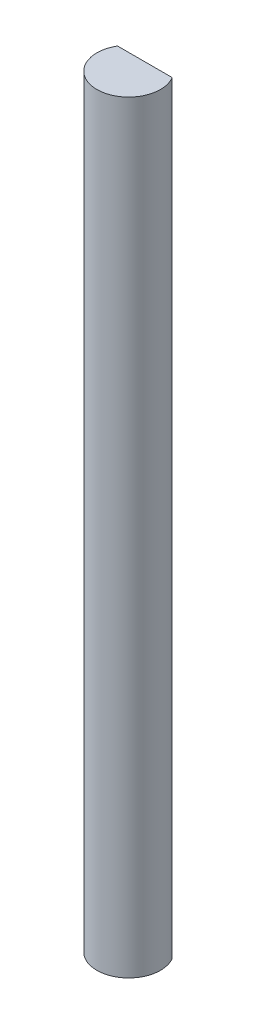
SolidWorks part; units mm, degrees
ref_plane "Front Plane" through (0, 0, 0) normal (0, 0, 1) x (1, 0, 0)
ref_plane "Top Plane" through (0, 0, 0) normal (0, 1, 0) x (1, 0, 0)
ref_plane "Right Plane" through (0, 0, 0) normal (1, 0, 0) x (0, 0, -1)
sketch "Sketch1" plane through (0, 0, 0) normal (0, 1, 0) x (1, 0, 0)
  line L0 (-2.7309, 1.6195) -> (2.7309, 1.6195)
  circle A0 centre (0, 0) radius 3.175
  dimension "D1" = 6.35
  dimension "D2" = 1.6195
extrude "Boss-Extrude1" add sketch "Sketch1" along normal blind 76.2 contours L0 A0 region at (0, 0, 0.5293)
